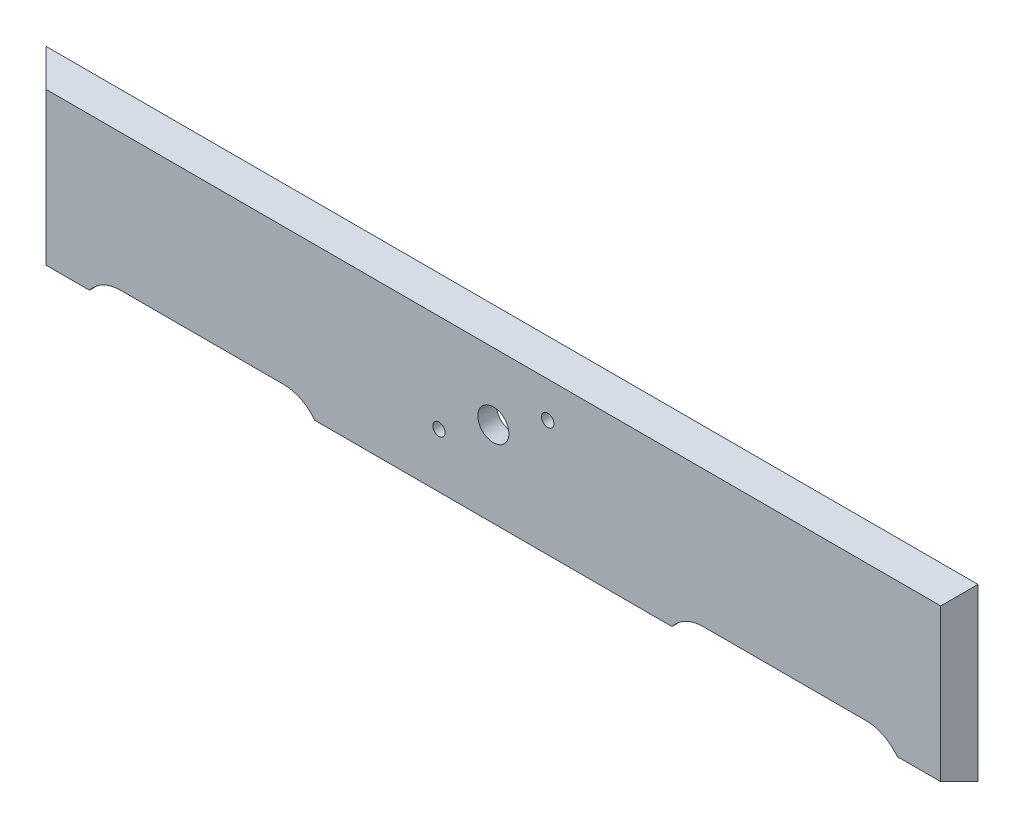
SolidWorks part; units mm, degrees
material "Teak"
ref_plane "Front Plane" through (0, 0, 0) normal (0, 0, 1) x (1, 0, 0)
ref_plane "Top Plane" through (0, 0, 0) normal (0, 1, 0) x (1, 0, 0)
ref_plane "Right Plane" through (0, 0, 0) normal (1, 0, 0) x (0, 0, -1)
sketch "Sketch1" plane through (0, 0, 0) normal (0, 0, 1) x (1, 0, 0)
  line L0 (0, 0) -> (0, -10)
  line L1 (60, 0) -> (165, 0)
  line L2 (0, 0) -> (0, 100)
  line L3 (0, 100) -> (600, 100)
  line L4 (600, 0) -> (600, 100)
  line L5 (0, -10) -> (40, -10)
  line L6 (600, 0) -> (600, -10)
  line L7 (600, -10) -> (560, -10)
  line L8 (300, 100) -> (300, -10) construction
  line L9 (185, -10) -> (415, -10)
  line L10 (435, 0) -> (540, 0)
  arc A0 (40, -10) -> (60, 0) centre (60, -25) cw
  arc A1 (560, -10) -> (540, 0) centre (540, -25) ccw
  arc A2 (185, -10) -> (165, 0) centre (165, -25) ccw
  arc A3 (415, -10) -> (435, 0) centre (435, -25) cw
  dimension "D7" = 25
  dimension "D8" = 25
  dimension "D13" = 25
  dimension "D14" = 25
  dimension "D1" = 600
  dimension "D2" = 100
  dimension "D3" = 10
  dimension "D4" = 10
  dimension "D5" = 40
  dimension "D6" = 40
  dimension "D9" = 10
  dimension "D10" = 10
  dimension "D11" = 115
  dimension "D12" = 115
extrude "Boss-Extrude1" add sketch "Sketch1" along normal blind 12
chamfer "Chamfer1" distance 12 angle 45 3 edges at (300, 100, 12) (600, 45, 12) (0, 45, 12)
sketch "Sketch2" plane through (0, 0, 0) normal (0, 0, -1) x (-1, 0, 0)
  line L0 (-600, 100) -> (0, 100) construction
  line L1 (-375, 90) -> (-225, 90)
  line L2 (-375, 90) -> (-375, 0)
  line L3 (-375, 0) -> (-225, 0)
  line L4 (-225, 90) -> (-225, 0)
  line L5 (-60, 0) -> (-165, 0) construction
  line L6 (-185, -10) -> (-415, -10) construction
  circle A0 centre (-335, 65) radius 4
  circle A1 centre (-265, 25) radius 4
  circle A2 centre (-300, 45) radius 10
  point P12 (-300, 100)
  point P13 (-300, 90)
  point P16 (0, 0)
  point P17 (-225, 45)
  dimension "D1" = 8
  dimension "D2" = 8
  dimension "D8" = 20
  dimension "D3" = 150
  dimension "D4" = 40
  dimension "D5" = 40
  dimension "D6" = 25
  dimension "D7" = 25
  dimension "D9" = 10
extrude "Cut-Extrude1" cut sketch "Sketch2" against normal through all contours A0 | A2 | A1 region at (335, 65, 0) region at (265, 25, 0) region at (300, 45, 0)
